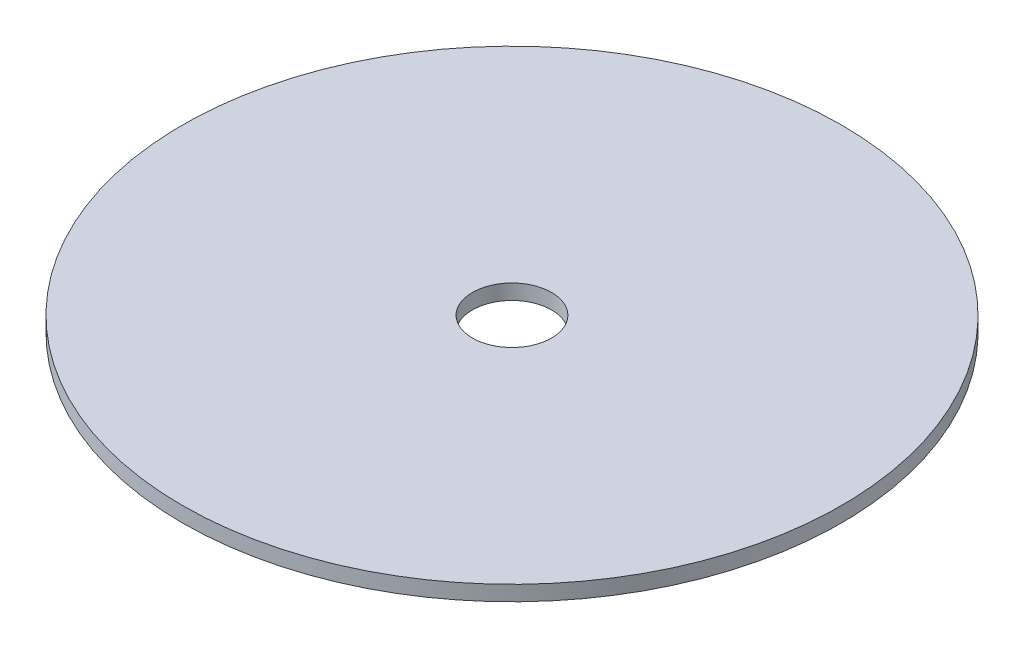
SolidWorks part; units mm, degrees
ref_plane "Front Plane" through (0, 0, 0) normal (0, 0, 1) x (1, 0, 0)
ref_plane "Top Plane" through (0, 0, 0) normal (0, 1, 0) x (1, 0, 0)
ref_plane "Right Plane" through (0, 0, 0) normal (1, 0, 0) x (0, 0, -1)
sketch "Sketch1" plane through (0, 0, 0) normal (0, 1, 0) x (1, 0, 0)
  circle A0 centre (0, 0) radius 50
base flange "Base-Flange1" sketch "Sketch1" thickness 2.3 reverse thickness direction no parameters "D1"=1.6
sketch "Sketch6" plane through (0, 0, 0) normal (0, 1, 0) x (1, 0, 0)
  circle A0 centre (0, 0) radius 6
  dimension "D1" = 12
extrude "Cut-Extrude1" cut sketch "Sketch6" against normal blind 10 normal cut yes
sketch "Bend-Lines1" [suppressed] plane through (0, 0, 0) normal (0, 1, 0) x (1, 0, 0)
sketch "Bounding-Box1" [suppressed] plane through (0, 0, 0) normal (0, 1, 0) x (1, 0, 0)
sheet metal parameters "Sheet-Metal1" thickness 2.3 parameters "D1"=1.6
flat pattern "Flat-Pattern1" [suppressed]
sketch "Bend-Lines2" plane through (0, 0, 0) normal (0, 1, 0) x (1, 0, 0)
sketch3d "Bounding-Box2" [suppressed]
  line L0 (50.0306, 49.9694, 0) -> (49.9694, -50.0306, 0) construction
  line L1 (-49.9694, 50.0306, 0) -> (-50.0306, -49.9694, 0) construction
  line L2 (50.0306, 49.9694, 0) -> (-49.9694, 50.0306, 0) construction
  line L3 (49.9694, -50.0306, 0) -> (-50.0306, -49.9694, 0) construction
sheet metal parameters "Sheet-Metal2" thickness 2.3 parameters "D1"=1.6
flat pattern "Flat-Pattern1"
sketch "Bend-Lines2" plane through (0, 0, 0) normal (0, 1, 0) x (1, 0, 0)
sketch3d "Bounding-Box2" [suppressed]
  line L0 (-50.0306, 49.9694, 0) -> (-49.9694, -50.0306, 0) construction
  line L1 (49.9694, 50.0306, 0) -> (50.0306, -49.9694, 0) construction
  line L2 (-50.0306, 49.9694, 0) -> (49.9694, 50.0306, 0) construction
  line L3 (-49.9694, -50.0306, 0) -> (50.0306, -49.9694, 0) construction
